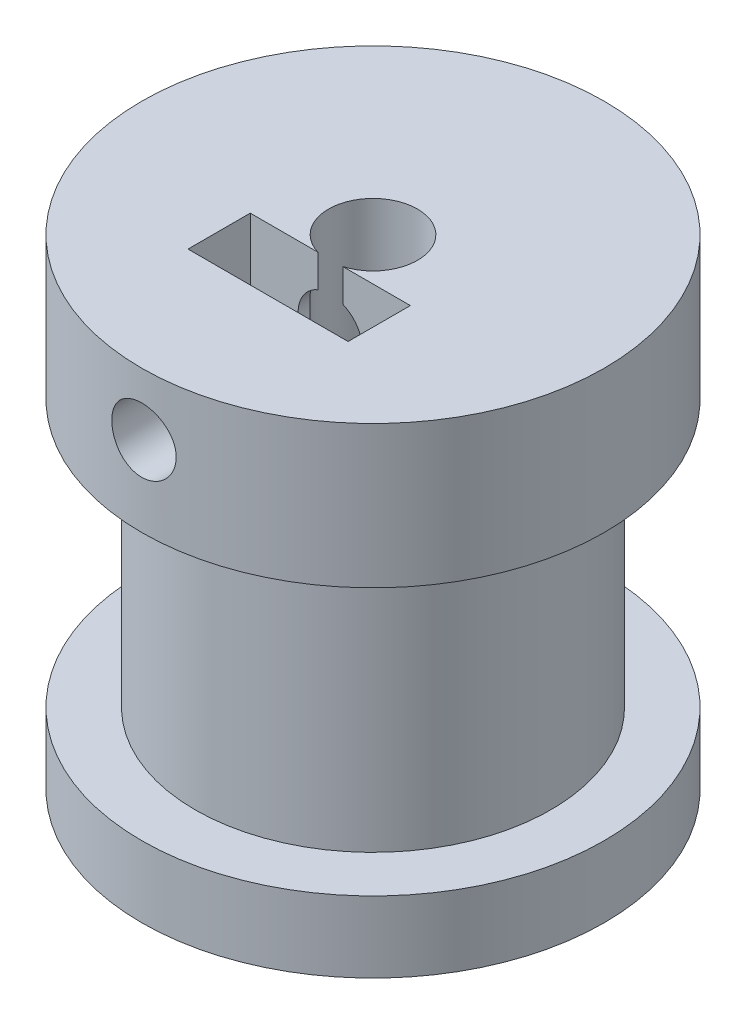
SolidWorks part; units mm, degrees
ref_plane "Front Plane" through (0, 0, 0) normal (0, 0, 1) x (1, 0, 0)
ref_plane "Top Plane" through (0, 0, 0) normal (0, 1, 0) x (1, 0, 0)
ref_plane "Right Plane" through (0, 0, 0) normal (1, 0, 0) x (0, 0, -1)
sketch "Sketch1" plane through (0, 0, 0) normal (0, 1, 0) x (1, 0, 0)
  circle A0 centre (0, 0) radius 10
  circle A1 centre (0, 0) radius 2.5
  dimension "D1" = 20
  dimension "D2" = 5
extrude "Boss-Extrude1" add sketch "Sketch1" along normal mid plane 15
sketch "Sketch2" plane through (0, 0, 0) normal (0, 1, 0) x (1, 0, 0)
  circle A1 centre (0, 0) radius 10 construction
  circle A2 centre (0, 0) radius 13
  circle A3 centre (0, 0) radius 10
  circle A5 centre (0, 0) radius 2.5 construction
  circle A6 centre (0, 0) radius 2.5
  dimension "D1" = 3
extrude "Boss-Extrude2" add sketch "Sketch2" along normal blind 8 from surface contours A2 A3 | A3 A6 region at (-12.6323, 0, 0) region at (-9.7172, 0, 0) starting at face at (0, 7.5, 10)
extrude "Boss-Extrude3" add sketch "Sketch2<4>" against normal blind 4 from surface contours A2 A3 | A3 A6 region at (-12.6323, 0, 0) region at (-9.7172, 0, 0) starting at face at (0, -7.5, 10)
sketch "Sketch2<4>" plane through (0, 0, 0) normal (0, 1, 0) x (1, 0, 0) same geometry as "Sketch2"
sketch "Sketch4" plane through (0, 15.5, 0) normal (0, 1, 0) x (1, 0, 0)
  line L1 (-4.5, -2.4) -> (4.5, -2.4)
  line L2 (-4.5, -2.4) -> (-4.5, -5.9)
  line L3 (-4.5, -5.9) -> (4.5, -5.9)
  line L4 (4.5, -2.4) -> (4.5, -5.9)
  point P4 (0, -2.4)
  point P8 (0, 0)
  dimension "D1" = 3.5
  dimension "D2" = 9
  dimension "D3" = 2.4
extrude "Cut-Extrude5" cut sketch "Sketch4" against normal blind 12 contours L2 L3 L4 L1
sketch "Sketch5" plane through (0, 0, 0) normal (0, 0, 1) x (1, 0, 0)
  circle A0 centre (0, 12) radius 1.81
  point P2 (0, 0)
  point P4 (0, 0)
  dimension "D1" = 3.62
  dimension "D2" = 12
extrude "Cut-Extrude7" cut sketch "Sketch5" along normal through all contours A0
